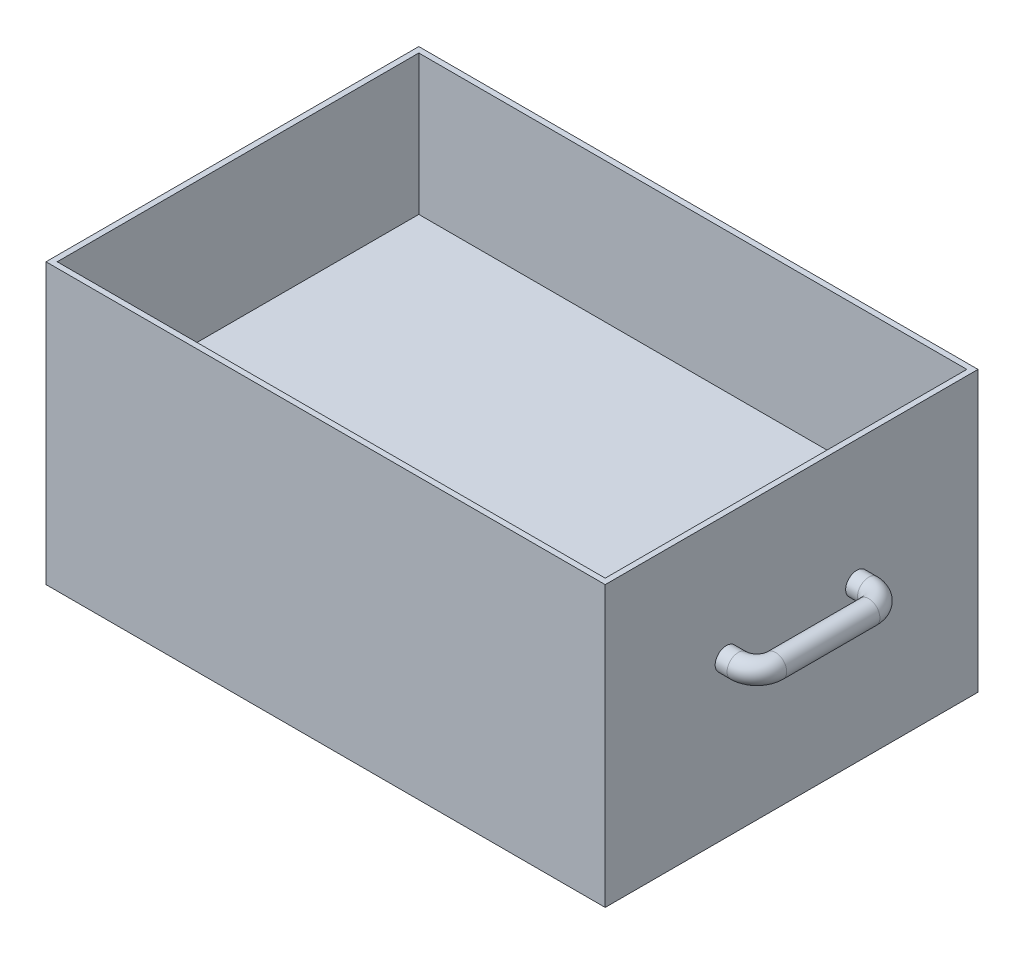
SolidWorks part; units mm, degrees
ref_plane "前视" through (0, 0, 0) normal (0, 0, 1) x (1, 0, 0)
ref_plane "上视" through (0, 0, 0) normal (0, 1, 0) x (1, 0, 0)
ref_plane "右视" through (0, 0, 0) normal (1, 0, 0) x (0, 0, -1)
sketch "Sketch1" plane through (0, 0, 0) normal (0, 1, 0) x (1, 0, 0)
  line L1 (-136.8201, 119.8745) -> (163.1799, 119.8745)
  line L2 (-136.8201, 119.8745) -> (-136.8201, -80.1255)
  line L3 (-136.8201, -80.1255) -> (163.1799, -80.1255)
  line L4 (163.1799, 119.8745) -> (163.1799, -80.1255)
  dimension "D1" = 300
  dimension "D2" = 200
extrude "Boss-Extrude1" add sketch "Sketch1" along normal blind 150
shell "Shell1" thickness 3 removed face at (13.1799, 150, -19.8745)
shell "Shell2" thickness 3 removed face at (13.1799, 0, -19.8745)
sketch "Sketch2" plane through (163.1799, 0, 0) normal (1, 0, 0) x (0, 0, -1)
  line L1 (-80.1255, 150) -> (-80.1255, 0) construction
  circle A0 centre (-15.1255, 83.1724) radius 6
  point P9 (54.8745, 83.1724)
  dimension "D2" = 65
ref_plane "Plane1" through (0, 83.1724, 0) normal (0, 1, 0) x (1, 0, 0)
sketch "Sketch4" plane through (0, 83.1724, 0) normal (0, 1, 0) x (1, 0, 0)
  line L0 (163.1799, -15.1255) -> (169.5656, -15.1255)
  line L1 (179.5656, -5.1255) -> (179.5656, 44.8745)
  line L2 (169.5656, 54.8745) -> (163.1799, 54.8745)
  arc A0 (179.5656, -5.1255) -> (169.5656, -15.1255) centre (169.5656, -5.1255) cw
  arc A1 (179.5656, 44.8745) -> (169.5656, 54.8745) centre (169.5656, 44.8745) ccw
  dimension "D1" = 10
sweep "Sweep2" add profiles "Sketch2" path "Sketch4"
